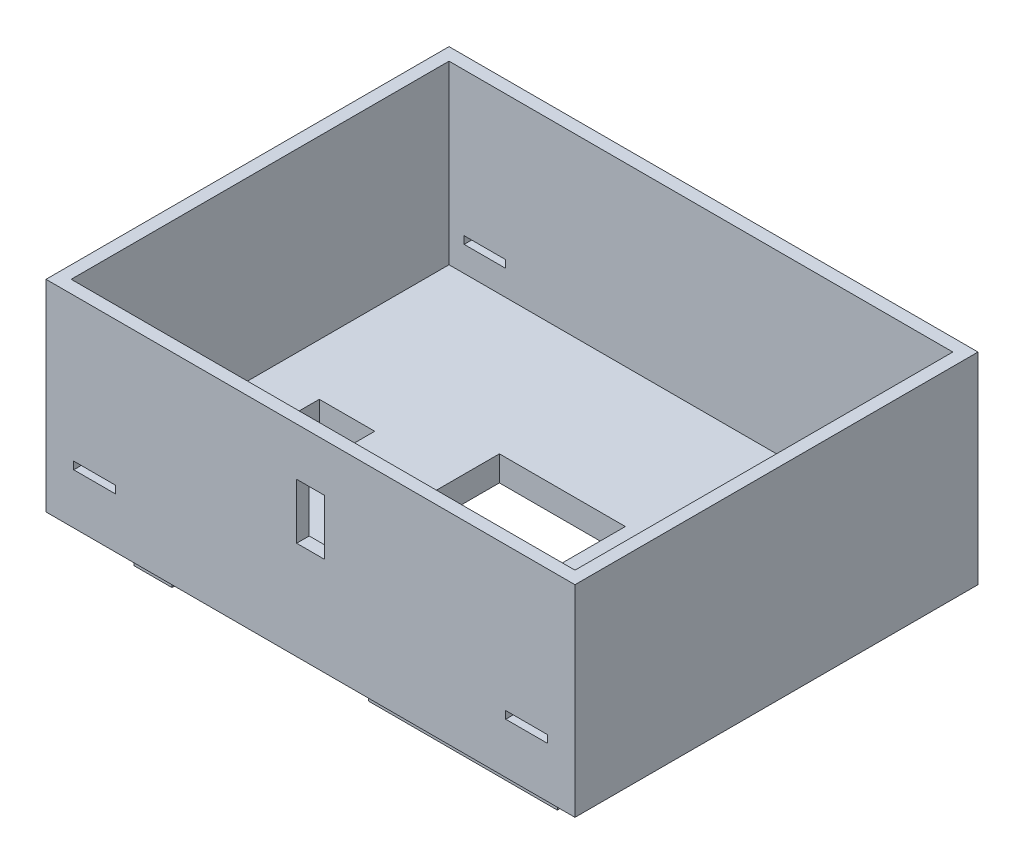
SolidWorks part; units mm, degrees
ref_plane "Front Plane" through (0, 0, 0) normal (0, 0, 1) x (1, 0, 0)
ref_plane "Top Plane" through (0, 0, 0) normal (0, 1, 0) x (1, 0, 0)
ref_plane "Right Plane" through (0, 0, 0) normal (1, 0, 0) x (0, 0, -1)
sketch "Sketch1" plane through (0, 0, 0) normal (0, 1, 0) x (1, 0, 0)
  line L0 (-100, -55) -> (100, -55) construction
  line L1 (-100, 75) -> (100, 75)
  line L2 (-100, 75) -> (-100, -75)
  line L3 (-100, -75) -> (100, -75)
  line L4 (100, 75) -> (100, -75)
  line L5 (-100, 75) -> (100, -75) construction
  line L6 (-100, -75) -> (100, 75) construction
  line L7 (84, -66) -> (9, -66)
  line L8 (-84, -61) -> (-69, -61)
  line L9 (-84, -44) -> (-69, -44)
  line L10 (-84, -44) -> (-84, -49)
  line L11 (-84, -49) -> (-69, -49)
  line L12 (-69, -44) -> (-69, -49)
  line L13 (-69, -66) -> (-69, -61)
  line L14 (-84, -66) -> (-69, -66)
  line L15 (-84, -66) -> (-84, -61)
  line L24 (84, -49) -> (9, -49)
  line L25 (84, -49) -> (84, -44)
  line L26 (84, -44) -> (9, -44)
  line L27 (9, -49) -> (9, -44)
  line L28 (84, -49) -> (9, -44) construction
  line L29 (84, -44) -> (9, -49) construction
  line L30 (9, -61) -> (9, -66)
  line L31 (84, -61) -> (9, -61)
  line L32 (84, -61) -> (84, -66)
  line L33 (-100, 0) -> (100, 0) construction
  line L34 (84, 44) -> (9, 44)
  line L35 (9, 49) -> (9, 44)
  line L36 (84, 49) -> (9, 49)
  line L37 (84, 49) -> (84, 44)
  line L38 (84, 61) -> (84, 66)
  line L39 (84, 61) -> (9, 61)
  line L40 (9, 61) -> (9, 66)
  line L41 (84, 66) -> (9, 66)
  line L42 (-84, 66) -> (-84, 61)
  line L43 (-84, 66) -> (-69, 66)
  line L44 (-69, 66) -> (-69, 61)
  line L45 (-84, 61) -> (-69, 61)
  line L46 (-84, 49) -> (-69, 49)
  line L47 (-69, 44) -> (-69, 49)
  line L48 (-84, 44) -> (-69, 44)
  line L49 (-84, 44) -> (-84, 49)
  point P0 (0, 0)
  point P8 (46.5, -46.5)
  point P25 (84, -63.5)
  dimension "D1" = 150
  dimension "D2" = 200
  dimension "D3" = 16
  dimension "D4" = 5
  dimension "D5" = 6
  dimension "D6" = 15
  dimension "D7" = 5
  dimension "D8" = 75
  dimension "D9" = 6
  dimension "D10" = 16
  dimension "D11" = 20
extrude "Boss-Extrude2" add sketch "Sketch1" against normal blind 10
extrude "Boss-Extrude3" add sketch "Sketch1<8>" against normal blind 25 contours L49 L48 L47 L46 | L42 L45 L44 L43 | L38 L41 L40 L39 | L37 L36 L35 L34 | L9 L12 L11 L10 | L8 L13 L14 L15 | L24 L27 L26 L25 | L31 L30 L7 L32 region at (46.5, 0, -46.5) region at (46.5, 0, -63.5) region at (-76.5, 0, -63.5) region at (-76.5, 0, -46.5)
sketch "Sketch1<8>" plane through (0, 0, 0) normal (0, 1, 0) x (1, 0, 0) same geometry as "Sketch1"
sketch "Sketch5" plane through (0, 0, 0) normal (0, 1, 0) x (-1, 0, 0)
  line L0 (-100, -75) -> (100, -75) construction
  line L2 (100, 75) -> (100, -75)
  line L3 (100, -75) -> (105, -75)
  line L4 (105, 70.0971) -> (105, -75)
  line L7 (-100, 75) -> (-100, -75)
  line L8 (-100, -75) -> (-105, -75)
  line L9 (-105, 70.0971) -> (-105, -75)
  line L10 (-100, 75) -> (100, 75)
  line L11 (-105, 70.0971) -> (-105, 80)
  line L12 (-105, 80) -> (105, 80)
  line L13 (105, 70.0971) -> (105, 80)
  dimension "D1" = 5
  dimension "D2" = 5
  dimension "D3" = 5
extrude "Boss-Extrude4" add sketch "Sketch5" along normal blind 80 from offset 10 offset against normal yes
sketch "Sketch7" plane through (0, 0, 44) normal (0, 0, -1) x (-1, 0, 0)
  line L0 (69, -25) -> (84, -10) construction
  line L1 (84, -25) -> (69, -10) construction
  circle A0 centre (76.5, -17.5) radius 5
  dimension "D1" = 10
extrude "Cut-Extrude2" cut sketch "Sketch7" against normal through all both and the other way through all
sketch "Sketch8" plane through (0, 0, 66) normal (0, 0, 1) x (1, 0, 0)
  line L0 (16.5, -17.5) -> (76.5, -17.5) construction
  line L1 (16.5, -12.5) -> (76.5, -12.5)
  line L2 (16.5, -22.5) -> (76.5, -22.5)
  line L3 (84, -25) -> (84, -10) construction
  line L6 (9, -10) -> (84, -25) construction
  line L7 (84, -10) -> (9, -25) construction
  line L8 (9, -25) -> (9, -10) construction
  arc A0 (16.5, -12.5) -> (16.5, -22.5) centre (16.5, -17.5) ccw
  arc A1 (76.5, -22.5) -> (76.5, -12.5) centre (76.5, -17.5) ccw
  point P2 (46.5, -17.5)
  point P21 (46.5, -17.5)
  dimension "D2" = 5
  dimension "D1" = 7.5
  dimension "D3" = 7.5
extrude "Cut-Extrude3" cut sketch "Sketch8" against normal through all
sketch "Sketch9" plane through (0, 0, 80) normal (0, 0, 1) x (1, 0, 0)
  line L0 (-105, 30) -> (105, 30) construction
  line L1 (-105, 70) -> (-105, -10) construction
  line L2 (105, 70) -> (105, -10) construction
  line L7 (-5.5, 51) -> (5.5, 51)
  line L8 (-5.5, 51) -> (-5.5, 29)
  line L9 (-5.5, 29) -> (5.5, 29)
  line L10 (5.5, 51) -> (5.5, 29)
  line L11 (-5.5, 40) -> (5.5, 40) construction
  line L12 (0, 70) -> (0, -10) construction
  line L13 (-105, 70) -> (105, 70) construction
  line L14 (-105, -10) -> (105, -10) construction
  line L15 (0, 51) -> (0, 29) construction
  dimension "D1" = 11
  dimension "D2" = 22
  dimension "D3" = 10
extrude "Cut-Extrude4" cut sketch "Sketch9" against normal blind 10
sketch "Sketch15" plane through (0, -10, 0) normal (0, -1, 0) x (1, 0, 0)
  line L0 (-105, 2.5) -> (105, 2.5) construction
  line L1 (-105, -75) -> (-105, 80) construction
  line L2 (105, 80) -> (105, -75) construction
  line L3 (0, 80) -> (0, -75) construction
  line L4 (-79.5, 8) -> (-57.5, 8)
  line L5 (-79.5, 8) -> (-79.5, -3)
  line L6 (-79.5, -3) -> (-57.5, -3)
  line L7 (-57.5, 8) -> (-57.5, -3)
  line L8 (-79.5, 8) -> (-57.5, -3) construction
  line L9 (-79.5, -3) -> (-57.5, 8) construction
  line L10 (-105, 80) -> (105, 80) construction
  line L11 (105, -75) -> (-105, -75) construction
  line L12 (79.5, -3) -> (57.5, -3)
  line L13 (57.5, 8) -> (57.5, -3)
  line L14 (79.5, 8) -> (57.5, 8)
  line L15 (79.5, 8) -> (79.5, -3)
  line L17 (-25, 20) -> (25, 20)
  line L18 (-25, 20) -> (-25, -20)
  line L19 (-25, -20) -> (25, -20)
  line L20 (25, 20) -> (25, -20)
  line L21 (-25, 20) -> (25, -20) construction
  line L22 (-25, -20) -> (25, 20) construction
  point P6 (-68.5, 2.5)
  point P21 (0, 0)
  dimension "D1" = 11
  dimension "D2" = 22
  dimension "D3" = 25.5
  dimension "D4" = 40
  dimension "D5" = 50
extrude "Cut-Extrude9" cut sketch "Sketch15" against normal blind 10
sketch "Sketch17" plane through (0, 0, 75) normal (0, 0, -1) x (-1, 0, 0)
  line L0 (-100, 70) -> (-100, 0) construction
  line L1 (-94, 13) -> (-77.5, 13)
  line L2 (-94, 13) -> (-94, 10)
  line L3 (-94, 10) -> (-77.5, 10)
  line L4 (-77.5, 13) -> (-77.5, 10)
  line L6 (100, 0) -> (-100, 0) construction
  line L7 (0, 70) -> (0, 0) construction
  line L8 (-100, 70) -> (100, 70) construction
  line L9 (77.5, 13) -> (77.5, 10)
  line L10 (94, 10) -> (77.5, 10)
  line L11 (94, 13) -> (94, 10)
  line L12 (94, 13) -> (77.5, 13)
  dimension "D1" = 6
  dimension "D2" = 10
  dimension "D3" = 16.5
  dimension "D4" = 3
sketch "Sketch18" plane through (0, 0, 0) normal (0, 1, 0) x (1, 0, 0)
  line L0 (105, -80) -> (105, 75) construction
  line L1 (-105, 75) -> (105, 75)
  line L2 (-105, 75) -> (-105, 80)
  line L3 (-105, 80) -> (105, 80)
  line L4 (105, 75) -> (105, 80)
  dimension "D1" = 5
extrude "Boss-Extrude9" add sketch "Sketch18" along normal up to surface (70 mm away) from offset 10 up to face at (0, 70, 1.25) offset against normal yes
extrude "Cut-Extrude11" cut sketch "Sketch17" against normal through all both and the other way through all contours L1 L4 L3 L2 | L12 L9 L10 L11
